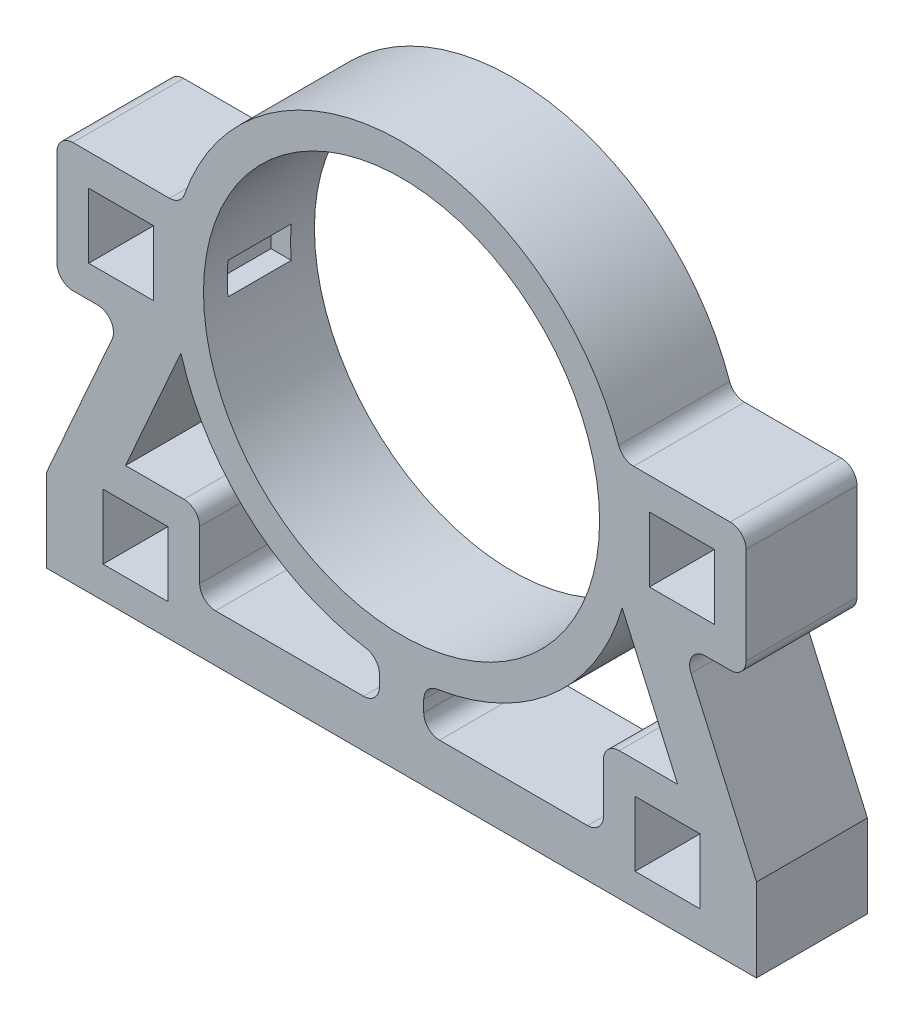
SolidWorks part; units mm, degrees
material "1023 Carbon Steel Sheet (SS)"
ref_plane "Ön Düzlem" through (0, 0, 0) normal (0, 0, 1) x (1, 0, 0)
ref_plane "Üst Düzlem" through (0, 0, 0) normal (0, 1, 0) x (1, 0, 0)
ref_plane "Sağ Düzlem" through (0, 0, 0) normal (1, 0, 0) x (0, 0, -1)
sketch "Sketch1" plane through (0, 0, 0) normal (0, 0, 1) x (1, 0, 0)
  line L0 (-7, -72.1613) -> (-7, -85.1613)
  line L1 (-7, -85.1613) -> (7, -85.1613)
  line L2 (94.2084, -90.1613) -> (73.7084, -69.6613) construction
  line L3 (94.2084, -69.6613) -> (73.7084, -90.1613) construction
  line L4 (-7, -85.1613) -> (-117, -85.1613)
  line L6 (-117, -85.1613) -> (-117, -100.1613)
  line L8 (-117, -100.1613) -> (117, -100.1613)
  line L13 (0, -100.1613) -> (0, -85.1613)
  line L14 (63.7084, -85.1613) -> (63.7084, -59.6613)
  line L15 (63.7084, -59.6613) -> (105.7084, -59.6613)
  line L16 (94.2084, -69.6613) -> (73.7084, -69.6613)
  line L17 (-117, -85.1613) -> (-66.2915, 29.3544)
  line L20 (-63.7084, -85.1613) -> (-63.7084, -59.6613)
  line L21 (-63.7084, -59.6613) -> (-105.7084, -59.6613)
  line L22 (-92.6994, -72.2698) -> (-69.6344, -20.1817)
  line L23 (94.2084, -90.1613) -> (94.2084, -69.6613)
  line L28 (-69.6344, -20.1817) -> (-108.7348, -20.1817)
  line L29 (-94.2084, -90.1613) -> (-73.7084, -90.1613)
  line L30 (94.2084, -90.1613) -> (73.7084, -90.1613)
  line L31 (73.7084, -90.1613) -> (73.7084, -69.6613)
  line L32 (7, -85.1613) -> (117, -85.1613)
  line L37 (7, -72.1613) -> (7, -85.1613)
  line L38 (117, -85.1613) -> (117, -100.1613)
  line L39 (-94.2084, -90.1613) -> (-94.2084, -69.6613)
  line L40 (-94.2084, -69.6613) -> (-73.7084, -69.6613)
  line L41 (-73.7084, -90.1613) -> (-73.7084, -69.6613)
  line L42 (-94.2084, -90.1613) -> (-73.7084, -69.6613) construction
  line L43 (-94.2084, -69.6613) -> (-73.7084, -90.1613) construction
  line L44 (-108.7348, -20.1817) -> (-108.7348, 20.3183)
  line L45 (-108.7348, 20.3183) -> (-69.5947, 20.3183)
  line L46 (0, -55) -> (0, 55) construction
  line L47 (-98.7348, -10.1817) -> (-78.2348, -10.1817)
  line L48 (-98.7348, -10.1817) -> (-98.7348, 10.3183)
  line L49 (-98.7348, 10.3183) -> (-78.2348, 10.3183)
  line L50 (-78.2348, -10.1817) -> (-78.2348, 10.3183)
  line L51 (-98.7348, -10.1817) -> (-78.2348, 10.3183) construction
  line L52 (-98.7348, 10.3183) -> (-78.2348, -10.1817) construction
  line L53 (98.7348, -10.1817) -> (78.2348, 10.3183) construction
  line L54 (98.7348, 10.3183) -> (78.2348, -10.1817) construction
  line L55 (108.7348, 20.3183) -> (69.5947, 20.3183)
  line L56 (108.7348, -20.1817) -> (108.7348, 20.3183)
  line L57 (98.7348, -10.1817) -> (98.7348, 10.3183)
  line L58 (69.6344, -20.1817) -> (108.7348, -20.1817)
  line L59 (78.2348, -10.1817) -> (78.2348, 10.3183)
  line L60 (78.2348, 10.3183) -> (98.7348, 10.3183)
  line L61 (98.7348, -10.1817) -> (78.2348, -10.1817)
  line L62 (117, -85.1613) -> (66.2915, 29.3544)
  line L63 (92.6994, -72.2698) -> (69.6344, -20.1817)
  circle A0 centre (0, 0) radius 62.5
  circle A1 centre (0, 0) radius 72.5
  point P9 (-94.2084, -79.9113)
  point P10 (83.9584, -79.9113)
  point P25 (-85, -85.1613)
  point P28 (-83.9584, -79.9113)
  point P38 (94.2084, -79.9113)
  point P43 (-88.4848, 0.0683)
  dimension "D1" = 125
  dimension "D2" = 10
  dimension "D6" = 10
  dimension "D7" = 17
  dimension "D11" = 20.5
  dimension "D3" = 15
  dimension "D4" = 13
  dimension "D5" = 110
  dimension "D8" = 25.5
  dimension "D9" = 10
  dimension "D10" = 20.5
  dimension "D13" = 100.1613
  dimension "D19" = 40.5
  dimension "D20" = 39.1401
  dimension "D21" = 20.5
  dimension "D22" = 20.5
  dimension "D23" = 10
  dimension "D24" = 10
  dimension "D25" = 42
ref_plane "Plane6" through (61.7, 0, 0) normal (1, 0, 0) x (0, 0, -1)
ref_plane "Plane7" through (-61.7, 0, 0) normal (1, 0, 0) x (0, 0, -1)
extrude "Boss-Extrude1" add sketch "Sketch1" along normal blind 35 contours A1 A0 | L50 L17 L45 L44 L28 L47 L48 L49 | A1 L45 L17 L50 L47 L28 | L22 L28 L17 L21 | L39 L40 L22 L21 L17 L4 | L41 L29 L39 L4 L6 L8 L13 L1 | L41 L4 L20 L21 L22 L40 | A1 L0 L1 L37 | L38 L32 L23 L30 L31 L1 L13 L8 | L16 L63 L15 L14 L32 L31 | L63 L16 L23 L32 L62 L15 | L63 L15 L62 L58 | A1 L58 L62 L61 L59 L55 | L62 L58 L56 L55 L59 L60 L57 L61 region at (0, -78.7738, 0) region at (-44.9903, -54.2124, 0) region at (-56.9209, -92.9714, 0) region at (-87.6714, -39.9215, 0) region at (-76.7148, -7.9838, 0) region at (56.9209, -92.9714, 0) region at (-73.5951, -69.5568, 0) region at (-101.9379, -72.8164, 0) region at (-98.4807, -19.6233, 0) region at (76.7148, -7.9838, 0) region at (87.6714, -39.9215, 0) region at (73.5951, -69.5568, 0) region at (86.5231, -14.9556, 0) region at (101.9379, -72.8164, 0)
fillet "Fillet2" radius 5 16 edges at (-108.7348, 20.3183, 17.5) (-69.5947, 20.3183, 17.5) (-88.2265, -20.1817, 17.5) (-108.7348, -20.1817, 17.5) (-63.7084, -85.1613, 17.5) (-63.7084, -59.6613, 17.5) (7, -85.1613, 17.5) (7, -72.1613, 17.5) (-7, -85.1613, 17.5) (-7, -72.1613, 17.5) (63.7084, -85.1613, 17.5) (63.7084, -59.6613, 17.5) (88.2265, -20.1817, 17.5) (108.7348, -20.1817, 17.5) (69.5947, 20.3183, 17.5) (108.7348, 20.3183, 17.5)
sketch "Sketch2" plane through (61.7, 0, 0) normal (1, 0, 0) x (0, 0, -1)
  line L0 (-35, -10.1817) -> (0, -10.1817) construction
  line L1 (-7.5, -4.9317) -> (-27.5, -4.9317)
  line L2 (-7.5, -4.9317) -> (-7.5, 5.0683)
  line L3 (-7.5, 5.0683) -> (-27.5, 5.0683)
  line L4 (-27.5, -4.9317) -> (-27.5, 5.0683)
  line L5 (-7.5, -4.9317) -> (-27.5, 5.0683) construction
  line L6 (-7.5, 5.0683) -> (-27.5, -4.9317) construction
  line L7 (0, -10.1817) -> (0, 10.3183) construction
  point P0 (-17.5, 0.0683)
  dimension "D1" = 20
  dimension "D2" = 10
  dimension "D3" = 5.25
  dimension "D4" = 7.5
extrude "Cut-Extrude2" cut sketch "Sketch2" along normal blind 7
sketch "Sketch3" plane through (-61.7, 0, 0) normal (1, 0, 0) x (0, 0, -1)
  line L0 (0, -10.1817) -> (0, 10.3183) construction
  line L1 (-27.5, -4.9317) -> (-7.5, -4.9317)
  line L2 (-27.5, -4.9317) -> (-27.5, 5.0683)
  line L3 (-27.5, 5.0683) -> (-7.5, 5.0683)
  line L4 (-7.5, -4.9317) -> (-7.5, 5.0683)
  line L5 (-27.5, -4.9317) -> (-7.5, 5.0683) construction
  line L6 (-27.5, 5.0683) -> (-7.5, -4.9317) construction
  line L7 (-35, -10.1817) -> (0, -10.1817) construction
  point P0 (-17.5, 0.0683)
  dimension "D1" = 20
  dimension "D2" = 10
  dimension "D3" = 7.5
  dimension "D4" = 5.25
extrude "Cut-Extrude3" cut sketch "Sketch3" against normal blind 7
sketch "Sketch4" plane through (117, 0, 0) normal (1, 0, 0) x (0, 0, -1)
  line L0 (0, -85.1613) -> (0, -27.2061) construction
  line L1 (-35, -100.1613) -> (0, -100.1613)
  line L2 (-35, -100.1613) -> (-35, -73.9177)
  line L3 (-35, -73.9177) -> (0, -73.9177)
  line L4 (0, -100.1613) -> (0, -73.9177)
  dimension "D1" = 26.2436
extrude "Cut-Extrude4" cut sketch "Sketch4" against normal blind 5
sketch "Sketch5" plane through (-117, 0, 0) normal (-1, 0, 0) x (0, 0, 1)
  line L0 (35, -85.1613) -> (35, -27.2061) construction
  line L1 (0, -100.1613) -> (35, -100.1613)
  line L2 (0, -100.1613) -> (0, -73.9213)
  line L3 (0, -73.9213) -> (35, -73.9213)
  line L4 (35, -100.1613) -> (35, -73.9213)
  dimension "D1" = 26.24
extrude "Cut-Extrude5" cut sketch "Sketch5" against normal blind 5
